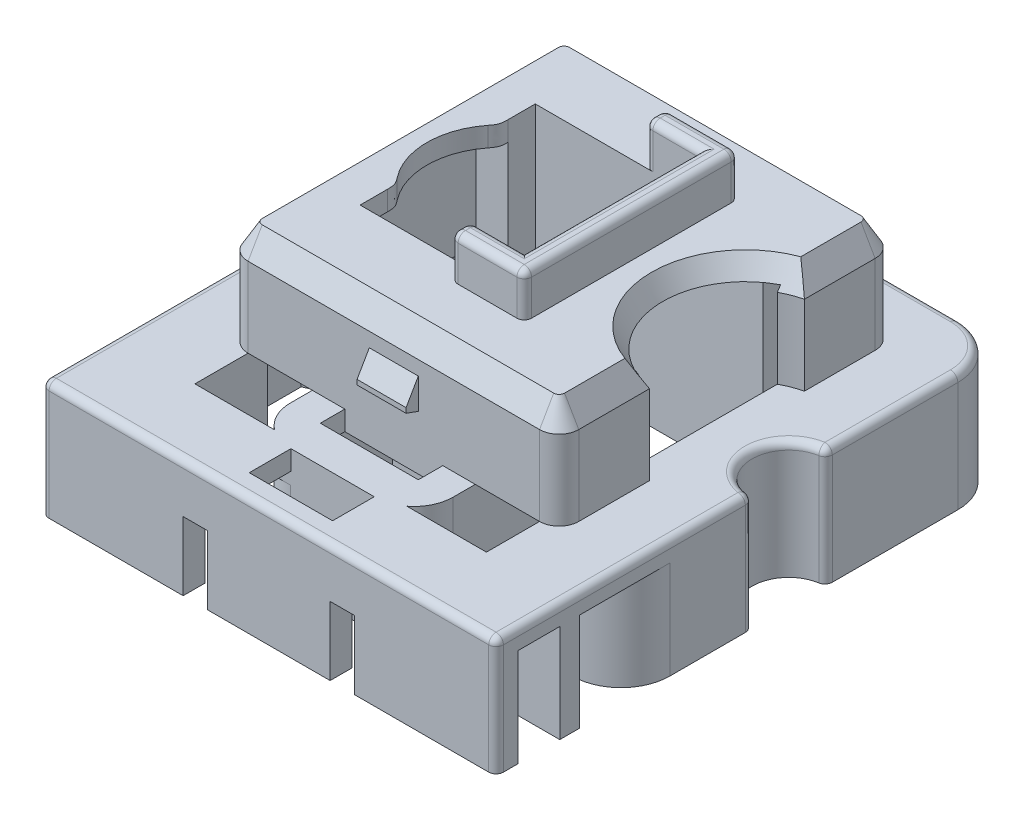
SolidWorks part; units mm, degrees
ref_plane "Front Plane" through (0, 0, 0) normal (0, 0, 1) x (1, 0, 0)
ref_plane "Top Plane" through (0, 0, 0) normal (0, 1, 0) x (1, 0, 0)
ref_plane "Right Plane" through (0, 0, 0) normal (1, 0, 0) x (0, 0, -1)
ref_plane "Floor" through (0, -4, 0) normal (0, -1, 0) x (-1, 0, 0)
sketch "Sketch1" plane through (0, 0, 0) normal (0, 1, 0) x (1, 0, 0)
  line L0 (9.275, -1.5) -> (9.275, -11.95)
  line L1 (-9.275, 8.9) -> (9.275, 8.9)
  line L2 (-9.275, 8.9) -> (-9.275, 1.5)
  line L3 (-9.275, -11.95) -> (9.275, -11.95)
  line L4 (9.275, 8.9) -> (9.275, 1.5)
  line L5 (-9.275, 8.9) -> (9.275, -11.95) construction
  line L6 (-9.275, -11.95) -> (9.275, 8.9) construction
  line L7 (-9.275, -1.5) -> (-9.275, -11.95)
  arc A0 (9.275, 1.5) -> (9.275, -1.5) centre (9.275, 0) ccw
  arc A1 (-9.275, -1.5) -> (-9.275, 1.5) centre (-9.275, 0) ccw
  point P0 (0, -1.525)
  dimension "D4" = 3
  dimension "D5" = 3
  dimension "D1" = 18.55
  dimension "D2" = 20.85
  dimension "D3" = 8.9
extrude "Boss-Extrude1" add sketch "Sketch1" along normal blind 0.8
sketch "Sketch2" plane through (0, 0.8, 0) normal (0, 1, 0) x (1, 0, 0)
  line L0 (6.75, -3.1623) -> (6.75, -6.85)
  line L1 (-6.75, 6.85) -> (6.75, 6.85)
  line L2 (-6.75, 6.85) -> (-6.75, -6.85)
  line L3 (-6.75, -6.85) -> (6.75, -6.85)
  line L4 (6.75, 6.85) -> (6.75, 3.1623)
  line L5 (-6.75, 6.85) -> (6.75, -6.85) construction
  line L6 (-6.75, -6.85) -> (6.75, 6.85) construction
  arc A0 (6.75, 3.1623) -> (6.75, -3.1623) centre (7.5, 0) ccw
  point P0 (0, 0)
  point P7 (13.3281, 0.717)
  point P12 (7.5, 0)
  dimension "D3" = 6.5
  dimension "D1" = 13.5
  dimension "D2" = 13.7
  dimension "D4" = 7.5
extrude "Boss-Extrude2" add sketch "Sketch2" along normal blind 4.25
sketch "Sketch15" plane through (0, 0, 0) normal (0, -1, 0) x (1, 0, 0)
  line L1 (5.95, 6.05) -> (-5.95, 6.05)
  line L2 (5.95, 6.05) -> (5.95, -6.05)
  line L3 (5.95, -6.05) -> (-5.95, -6.05)
  line L4 (-5.95, 6.05) -> (-5.95, -6.05)
  line L5 (5.95, 6.05) -> (-5.95, -6.05) construction
  line L6 (5.95, -6.05) -> (-5.95, 6.05) construction
  point P0 (0, 0)
  dimension "D1" = 11.9
  dimension "D2" = 12.1
extrude "Cut-Extrude3" cut sketch "Sketch15" against normal blind 4.25
ref_plane "Plane2" through (0, 2.3, 0) normal (0, 1, 0) x (1, 0, 0)
sketch "Sketch23" plane through (0, 5.05, 0) normal (0, 1, 0) x (1, 0, 0)
  line L0 (0, -1000) -> (0, 49000) construction
  line L1 (1.9, -1001.0023) -> (1.9, 48998.9977) construction
  line L2 (-2.5, -1002.0635) -> (-2.5, 48997.9365) construction
  line L3 (-4.5, -1002.4785) -> (-4.5, 48997.5215) construction
  line L4 (-1000, 0) -> (49000, 0) construction
  line L6 (-4.65, 3.575) -> (2.05, 3.575)
  line L7 (-4.65, 3.575) -> (-4.65, -3.575)
  line L8 (-4.65, -3.575) -> (2.05, -3.575)
  line L9 (2.05, 3.575) -> (2.05, -3.575)
  line L10 (-4.65, 3.575) -> (2.05, -3.575) construction
  line L11 (-4.65, -3.575) -> (2.05, 3.575) construction
  point P10 (-1.3, 0)
  dimension "D1" = 1.9
  dimension "D2" = 2.5
  dimension "D3" = 2
  dimension "D4" = 7.15
  dimension "D5" = 0.15
  dimension "D6" = 0.15
extrude "Cut-Extrude6" cut sketch "Sketch23" against normal up to surface (0.8 mm away) up to face at (1.7, 4.25, 0)
sketch "Sketch26" plane through (0, 5.05, -5.05) normal (0, -1, 0) x (1, 0, 0)
  line L0 (-0.15, 8.625) -> (-0.15, 9.425)
  line L1 (-4.65, 8.625) -> (2.05, 8.625) construction
  line L2 (-0.15, 9.425) -> (2.85, 9.425)
  line L3 (2.85, 9.425) -> (2.85, 0.675)
  line L4 (2.85, 0.675) -> (-0.15, 0.675)
  line L5 (-0.15, 0.675) -> (-0.15, 1.475)
  line L6 (2.05, 1.475) -> (-4.65, 1.475) construction
  line L7 (-0.15, 1.475) -> (2.05, 1.475)
  line L8 (2.05, 1.475) -> (2.05, 8.625)
  line L9 (2.05, 8.625) -> (-0.15, 8.625)
  line L10 (-0.15, -995.3291) -> (-0.15, 49004.6709) construction
  line L11 (-4.65, 1.475) -> (-4.65, 8.625) construction
  dimension "D1" = 4.5
  dimension "D2" = 0.8
  dimension "D3" = 0.8
  dimension "D4" = 0.8
extrude "Boss-Extrude17" add sketch "Sketch26" against normal blind 1.75
sketch "Sketch5" plane through (0, 5.05, 0) normal (0, 1, 0) x (1, 0, 0)
  circle A0 centre (-2.5, 0) radius 2.75 construction
  circle A1 centre (7.5, 0) radius 2.75 construction
  circle A2 centre (-2.5, 0) radius 3
  point P0 (-2.5, 0)
  dimension "D2" = 5.5
  dimension "D4" = 0.25
  dimension "D1" = 2.5
  dimension "D3" = 10
extrude "Cut-Extrude7" cut sketch "Sketch5" against normal up to surface (0.8 mm away) up to face at (-1.3, 4.25, 0)
sketch "Sketch6" plane through (0, 0, 6.85) normal (0, 0, 1) x (1, 0, 0)
  line L0 (-6.75, 0.8) -> (6.75, 0.8) construction
  line L1 (-1, 2.6) -> (1, 2.6)
  line L2 (-1, 2.6) -> (-1, 2.4)
  line L3 (-1, 2.4) -> (1, 2.4)
  line L4 (1, 2.6) -> (1, 2.4)
  line L5 (-1, 2.6) -> (1, 2.4) construction
  line L6 (-1, 2.4) -> (1, 2.6) construction
  point P0 (0, 2.5)
  dimension "D1" = 1.6
  dimension "D2" = 0.2
  dimension "D3" = 2
extrude "Boss-Extrude4" add sketch "Sketch6" along normal blind 0.5
draft "Draft1" type of draft neutral plane draft angle 60 faces to draft 1 face at (0, 2.6, 7.1) neutral plane through (0, 0, 7.35) neutral plane normal (0, 0, 1) parameters "D1"=60
draft "Draft4" type of draft neutral plane draft angle 20 faces to draft 1 face at (0, 2.4, 7.1) neutral plane through (0, 0, 7.35) neutral plane normal (0, 0, 1) parameters "D1"=20
sketch "Sketch7" plane through (0, 0.8, 0) normal (0, 1, 0) x (1, 0, 0)
  line L0 (-6.75, -6.85) -> (6.75, -6.85) construction
  line L1 (-2, -6.85) -> (2, -6.85)
  line L2 (-2, -6.85) -> (-2, -7.85)
  line L3 (-2, -7.85) -> (2, -7.85)
  line L4 (2, -6.85) -> (2, -7.85)
  line L5 (-2, -6.85) -> (2, -7.85) construction
  line L6 (-2, -7.85) -> (2, -6.85) construction
  point P0 (0, -7.35)
  dimension "D1" = 1
  dimension "D2" = 4
extrude "Cut-Extrude1" cut sketch "Sketch7" against normal through all
mirror "Mirror1" about plane through (0, 0, 0) normal (0, 0, 1) of "Draft4", "Draft1", "Boss-Extrude4", "Cut-Extrude1"
sketch "Sketch8" plane through (0, 0, 0) normal (0, 1, 0) x (1, 0, 0)
  line L1 (9.275, -11.05) -> (-9.275, -11.05)
  line L2 (9.275, -11.05) -> (9.275, -11.95)
  line L3 (9.275, -11.95) -> (-9.275, -11.95)
  line L4 (-9.275, -11.05) -> (-9.275, -11.95)
  line L5 (9.275, -11.05) -> (-9.275, -11.95) construction
  line L6 (9.275, -11.95) -> (-9.275, -11.05) construction
  line L8 (-9.275, -11.95) -> (9.275, -11.95) construction
  point P0 (0, -11.5)
  dimension "D1" = 0.9
extrude "Boss-Extrude5" add sketch "Sketch8" against normal up to surface (4 mm away) up to plane "Floor"
sketch "Sketch9" plane through (0, -4, 0) normal (0, -1, 0) x (-1, 0, 0)
  line L0 (9.275, -11.95) -> (-9.275, -11.95) construction
  line L1 (-9.275, -11.05) -> (9.275, -11.05) construction
  line L7 (-2.5, -11.95) -> (-3.5, -11.95)
  line L8 (-2.5, -11.95) -> (-2.5, -11.05)
  line L9 (-2.5, -11.05) -> (-3.5, -11.05)
  line L10 (-3.5, -11.95) -> (-3.5, -11.05)
  line L11 (-2.5, -11.95) -> (-3.5, -11.05) construction
  line L12 (-2.5, -11.05) -> (-3.5, -11.95) construction
  point P5 (-3, -11.5)
  dimension "D1" = 1
  dimension "D2" = 2.5
extrude "Cut-Extrude2" cut sketch "Sketch9" against normal blind 2.8
mirror "Mirror2" about plane through (0, 0, 0) normal (1, 0, 0) of "Cut-Extrude2"
sketch "Sketch11" plane through (0, 0, 0) normal (0, -1, 0) x (1, 0, 0)
  line L0 (9.275, 11.05) -> (9.275, 1.5) construction
  line L1 (5.95, 9.35) -> (9.275, 9.35)
  line L2 (5.95, 9.35) -> (5.95, 6.05)
  line L3 (9.275, 8.55) -> (6.75, 8.55)
  line L4 (9.275, 9.35) -> (9.275, 8.55)
  line L5 (9.275, 11.05) -> (-9.275, 11.05) construction
  line L6 (6.75, 8.55) -> (6.75, 6.85)
  line L7 (6.75, 6.85) -> (7.275, 6.85)
  line L8 (9.275, 4.85) -> (9.275, 1.5)
  line L9 (5.95, 6.05) -> (7.275, 6.05)
  line L10 (8.475, 4.85) -> (8.475, 2.1564)
  line L11 (9.275, -1.5) -> (9.275, -8.9)
  line L12 (9.275, -1.5) -> (9.275, -8.9) construction
  line L13 (8.475, -8.9) -> (8.475, -2.1564)
  line L14 (9.275, -8.9) -> (-9.275, -8.9) construction
  line L15 (8.475, -8.9) -> (9.275, -8.9)
  line L16 (5.95, -6.05) -> (5.95, 6.05) construction
  line L17 (5.95, 6.05) -> (-5.95, 6.05) construction
  arc A0 (9.275, 1.5) -> (9.275, -1.5) centre (9.275, 0) ccw
  arc A1 (8.475, 2.1564) -> (8.475, -2.1564) centre (9.275, 0) ccw
  arc A2 (7.275, 6.05) -> (8.475, 4.85) centre (7.275, 4.85) cw
  arc A3 (7.275, 6.85) -> (9.275, 4.85) centre (7.275, 4.85) cw
  point P24 (9.275, 6.85)
  dimension "D4" = 3
  dimension "D5" = 4.6
  dimension "D10" = 1.2
  dimension "D11" = 2
  dimension "D1" = 1.7
  dimension "D2" = 0.8
  dimension "D6" = 0.8
  dimension "D7" = 0.8
  dimension "D8" = 0.8
  dimension "D12" = 0.8
extrude "Boss-Extrude6" add sketch "Sketch11" along normal up to surface (4 mm away) up to plane "Floor"
sketch "Sketch12" plane through (0, 0, 0) normal (0, -1, 0) x (1, 0, 0)
  line L1 (5.95, 11.05) -> (6.75, 11.05)
  line L2 (5.95, 11.05) -> (5.95, 9.35)
  line L3 (5.95, 9.35) -> (6.75, 9.35)
  line L4 (6.75, 11.05) -> (6.75, 9.35)
  line L5 (9.275, 11.05) -> (-9.275, 11.05) construction
  line L6 (9.275, 9.35) -> (5.95, 9.35) construction
  line L7 (5.95, 9.35) -> (5.95, 6.05) construction
  line L8 (6.75, 6.85) -> (6.75, 8.55) construction
extrude "Boss-Extrude7" add sketch "Sketch12" along normal blind 1.5
mirror "Mirror3" about plane through (0, 0, 0) normal (1, 0, 0) of "Boss-Extrude7", "Boss-Extrude6"
sketch "Sketch19" plane through (0, 0, 0) normal (0, -1, 0) x (1, 0, 0)
  line L0 (8.475, -8.9) -> (-8.475, -8.9) construction
  line L1 (-4.65, -3.575) -> (4.65, -3.575)
  line L2 (-4.65, -3.575) -> (-4.65, -8.9)
  line L3 (-4.65, -8.9) -> (4.65, -8.9)
  line L4 (4.65, -3.575) -> (4.65, -8.9)
  line L5 (-4.65, -3.575) -> (4.65, -8.9) construction
  line L6 (-4.65, -8.9) -> (4.65, -3.575) construction
  line L7 (-4.65, -3.575) -> (2.05, -3.575) construction
  line L8 (-3.85, -8.1) -> (3.85, -8.1)
  line L9 (-3.85, -8.1) -> (-3.85, -4.375)
  line L10 (-3.85, -4.375) -> (3.85, -4.375)
  line L11 (3.85, -8.1) -> (3.85, -4.375)
  line L12 (-3.85, -8.1) -> (3.85, -4.375) construction
  line L13 (-3.85, -4.375) -> (3.85, -8.1) construction
  line L14 (-4.65, -2.0922) -> (-4.65, -3.575) construction
  point P0 (0, -6.2375)
  point P7 (0, -8.9)
  point P9 (0, -6.2375)
  dimension "D3" = 0.8
  dimension "D4" = 0.8
sketch "Sketch13" plane through (0, 0, 0) normal (0, -1, 0) x (1, 0, 0)
  line L0 (8.475, -8.9) -> (-8.475, -8.9) construction
  line L1 (8.475, -8.1) -> (-8.475, -8.1)
  line L2 (8.475, -8.1) -> (8.475, -8.9)
  line L3 (8.475, -8.9) -> (-8.475, -8.9)
  line L4 (-8.475, -8.1) -> (-8.475, -8.9)
  line L5 (8.475, -8.1) -> (-8.475, -8.9) construction
  line L6 (8.475, -8.9) -> (-8.475, -8.1) construction
  point P0 (0, -8.5)
  point P7 (0, -8.9)
  dimension "D1" = 0.8
extrude "Boss-Extrude8" add sketch "Sketch13" along normal up to surface (4 mm away) up to plane "Floor"
fillet "Fillet6" radius 1 2 edges at (-4.65, 4.65, 2.0922) (-4.65, 4.65, -2.0922) conic rho 0.65
fillet "Fillet1" radius 1.2 2 edges at (8.475, -2, -8.1) (-8.475, -2, -8.1)
fillet "Fillet2" radius 2 2 edges at (9.275, -1.6, -8.9) (-9.275, -1.6, -8.9)
fillet "Fillet3" radius 0.3 30 edges at (9.275, 0.8, -4.2) (8.6892, 0.8, -8.3142) (0, 0.8, -8.9) (-8.6892, 0.8, -8.3142) (7.775, 0.8, 0) (-7.775, 0.8, 0) (-9.275, 0.8, 6.725) (0, 0.8, 11.95) (9.275, 0.8, 6.725) (-9.275, 0.8, -4.2) (-9.275, -1.6, -1.5) (-9.275, -1.6, 1.5) (9.275, -1.6, -1.5) (9.275, -1.6, 1.5) (-9.275, -1.6, 11.95) (9.275, -1.6, 11.95) (2.05, 6.8, 0) (0.95, 6.8, -3.575) (-0.15, 6.8, -3.975) (1.35, 6.8, -4.375) (2.85, 6.8, 0) (1.35, 6.8, 4.375) (-0.15, 6.8, 3.975) (0.95, 6.8, 3.575) (-0.15, 5.925, -3.575) (-0.15, 5.925, -4.375) (-0.15, 5.925, 3.575) (-0.15, 5.925, 4.375) (2.85, 5.925, -4.375) (2.85, 5.925, 4.375)
fillet "Fillet5" radius 0.8 4 edges at (-6.75, 2.925, -6.85) (6.75, 2.925, -6.85) (-6.75, 2.925, 6.85) (6.75, 2.925, 6.85)
chamfer "Chamfer1" distance 1 angle 30 10 edges at (6.5157, 5.05, -6.6157) (0, 5.05, -6.85) (-6.5157, 5.05, -6.6157) (-6.75, 5.05, 0) (-6.5157, 5.05, 6.6157) (6.75, 5.05, -4.6061) (0, 5.05, 6.85) (6.75, 5.05, 4.6061) (6.5157, 5.05, 6.6157) (4.25, 5.05, 0) first distance on face at (6.4328, 2.925, -6.5328) first distance on face at (0, 2.842, -6.85) first distance on face at (-6.4328, 2.925, -6.5328) first distance on face at (-6.75, 2.925, 0) first distance on face at (-6.4328, 2.925, 6.5328) first distance on face at (6.75, 2.925, -4.6061) first distance on face at (0, 1.6625, 6.85) first distance on face at (6.75, 2.925, 4.6061) first distance on face at (6.4328, 2.925, 6.5328) first distance on face at (5.8225, 2.725, 0)
sketch "Sketch14" plane through (0, 0, 0) normal (0, -1, 0) x (1, 0, 0)
  line L0 (9.275, 9.35) -> (6.75, 9.35) construction
  line L1 (-1.725, 9.35) -> (1.725, 9.35)
  line L2 (-3.325, 7.75) -> (-3.325, 3.575)
  line L3 (-3.325, 3.575) -> (3.325, 3.575)
  line L4 (3.325, 7.75) -> (3.325, 3.575)
  line L5 (-3.325, 9.35) -> (3.325, 3.575) construction
  line L6 (-3.325, 3.575) -> (3.325, 9.35) construction
  line L7 (2.05, 3.575) -> (-4.65, 3.575) construction
  line L8 (-1.725, 8.55) -> (1.725, 8.55)
  line L9 (-2.525, 7.75) -> (-2.525, 4.375)
  line L10 (-2.525, 4.375) -> (2.525, 4.375)
  line L11 (2.525, 7.75) -> (2.525, 4.375)
  line L12 (-2.525, 8.55) -> (2.525, 4.375) construction
  line L13 (-2.525, 4.375) -> (2.525, 8.55) construction
  arc A0 (-1.725, 9.35) -> (-3.325, 7.75) centre (-1.725, 7.75) ccw
  arc A1 (1.725, 9.35) -> (3.325, 7.75) centre (1.725, 7.75) cw
  arc A2 (-1.725, 8.55) -> (-2.525, 7.75) centre (-1.725, 7.75) ccw
  arc A3 (1.725, 8.55) -> (2.525, 7.75) centre (1.725, 7.75) cw
  point P0 (0, 6.4625)
  point P10 (0, 6.4625)
  dimension "D5" = 1.6
  dimension "D6" = 0.8
  dimension "D1" = 6.65
  dimension "D3" = 0.8
  dimension "D4" = 0.8
extrude "Boss-Extrude9" add sketch "Sketch14" along normal up to surface (4 mm away) up to plane "Floor"
sketch "Sketch16" plane through (0, 0, 0) normal (0, -1, 0) x (1, 0, 0)
  line L8 (-3.325, 6.05) -> (-3.325, 3.575)
  line L9 (-2.525, 6.05) -> (-3.325, 6.05)
  line L10 (-2.525, 4.375) -> (-2.525, 6.05)
  line L11 (2.525, 4.375) -> (-2.525, 4.375)
  line L12 (2.525, 6.05) -> (2.525, 4.375)
  line L13 (3.325, 6.05) -> (2.525, 6.05)
  line L14 (3.325, 3.575) -> (3.325, 6.05)
  line L15 (-3.325, 3.575) -> (3.325, 3.575)
  line L16 (-3.325, 6.05) -> (-3.325, 3.575)
  line L17 (-2.525, 6.05) -> (-3.325, 6.05)
  line L18 (-2.525, 4.375) -> (-2.525, 6.05)
  line L19 (2.525, 4.375) -> (-2.525, 4.375)
  line L20 (2.525, 6.05) -> (2.525, 4.375)
  line L21 (3.325, 6.05) -> (2.525, 6.05)
  line L22 (3.325, 3.575) -> (3.325, 6.05)
  line L23 (-3.325, 3.575) -> (3.325, 3.575)
  dimension "D1" = 0
extrude "Boss-Extrude10" add sketch "Sketch16" against normal up to surface (4.25 mm away) up to face at (-3.0281, 4.25, 0.2928)
sketch "Sketch17" plane through (0, 0, 0) normal (0, -1, 0) x (1, 0, 0)
  line L0 (5.95, 11.05) -> (-5.95, 11.05) construction
  line L1 (-1.7, 11.05) -> (1.7, 11.05)
  line L2 (-1.7, 11.05) -> (-1.7, 9.35)
  line L3 (-1.7, 9.35) -> (1.7, 9.35)
  line L4 (1.7, 11.05) -> (1.7, 9.35)
  line L5 (-1.7, 11.05) -> (1.7, 9.35) construction
  line L6 (-1.7, 9.35) -> (1.7, 11.05) construction
  line L7 (1.725, 9.35) -> (-1.725, 9.35) construction
  point P0 (0, 10.2)
  dimension "D1" = 3.4
extrude "Cut-Extrude4" cut sketch "Sketch17" against normal through all
sketch "Sketch18" plane through (0, 0, 11.05) normal (0, 0, -1) x (-1, 0, 0)
  line L1 (1.4, -3.1) -> (-1.4, -3.1)
  line L2 (1.4, -3.1) -> (1.4, -3.3)
  line L3 (1.4, -3.3) -> (-1.4, -3.3)
  line L4 (-1.4, -3.1) -> (-1.4, -3.3)
  line L5 (1.4, -3.1) -> (-1.4, -3.3) construction
  line L6 (1.4, -3.3) -> (-1.4, -3.1) construction
  line L7 (-6.75, -1.5) -> (-5.95, -1.5) construction
  point P0 (0, -3.2)
  dimension "D1" = 1.6
  dimension "D2" = 0.2
  dimension "D3" = 2.8
extrude "Boss-Extrude11" add sketch "Sketch18" along normal blind 0.25
draft "Draft2" type of draft neutral plane draft angle 60 faces to draft 1 face at (0, -3.3, 10.925) neutral plane through (0, 0, 10.8) neutral plane normal (0, 0, -1) parameters "D1"=60
draft "Draft3" type of draft neutral plane draft angle 20 faces to draft 1 face at (0, -3.1, 10.925) neutral plane through (0, 0, 10.8) neutral plane normal (0, 0, -1) parameters "D1"=20
ref_plane "Plane4" through (0, 0, 10.2) normal (0, 0, -1) x (-1, 0, 0)
mirror "Mirror4" about plane through (0, 0, 10.2) normal (0, 0, -1) of "Draft3", "Draft2", "Boss-Extrude11"
extrude "Boss-Extrude12" add sketch "Sketch19" along normal up to surface (4 mm away) up to plane "Floor"
sketch "Sketch20" plane through (0, 0, 0) normal (0, -1, 0) x (1, 0, 0)
  line L8 (4.65, -6.05) -> (4.65, -3.575)
  line L9 (3.85, -6.05) -> (4.65, -6.05)
  line L10 (3.85, -4.375) -> (3.85, -6.05)
  line L11 (-3.85, -4.375) -> (3.85, -4.375)
  line L12 (-3.85, -6.05) -> (-3.85, -4.375)
  line L13 (-4.65, -6.05) -> (-3.85, -6.05)
  line L14 (-4.65, -3.575) -> (-4.65, -6.05)
  line L15 (4.65, -3.575) -> (-4.65, -3.575)
  line L16 (4.65, -6.05) -> (4.65, -3.575)
  line L17 (3.85, -6.05) -> (4.65, -6.05)
  line L18 (3.85, -4.375) -> (3.85, -6.05)
  line L19 (-3.85, -4.375) -> (3.85, -4.375)
  line L20 (-3.85, -6.05) -> (-3.85, -4.375)
  line L21 (-4.65, -6.05) -> (-3.85, -6.05)
  line L22 (-4.65, -3.575) -> (-4.65, -6.05)
  line L23 (4.65, -3.575) -> (-4.65, -3.575)
  dimension "D1" = 0
extrude "Boss-Extrude13" add sketch "Sketch20" against normal up to surface (4.25 mm away) up to face at (-0.7856, 4.25, 1.1996)
sketch "Sketch21" plane through (0, 0, 0) normal (0, -1, 0) x (1, 0, 0)
  line L0 (2.7, 11.05) -> (2.7, 9.0186) construction
  line L1 (5.95, 11.05) -> (1.7, 11.05) construction
  line L2 (1.7, 9.35) -> (1.7, 11.05) construction
  line L3 (2.7, 9.0186) -> (5.95, 9.0186)
  line L9 (5.95, 11.05) -> (1.7, 11.05)
  line L10 (1.7, 11.05) -> (1.7, 9.35)
  line L11 (1.7, 9.35) -> (1.725, 9.35)
  line L12 (3.325, 7.75) -> (3.325, 6.05)
  line L13 (3.325, 6.05) -> (5.95, 6.05)
  line L14 (5.95, 6.05) -> (5.95, 11.05)
  line L18 (3.325, 7.75) -> (3.325, 6.05)
  line L19 (3.325, 6.05) -> (5.95, 6.05)
  line L20 (5.95, 6.05) -> (5.95, 9.0186)
  arc A0 (3.325, 7.75) -> (1.725, 9.35) centre (1.725, 7.75) ccw construction
  arc A2 (3.325, 7.75) -> (1.725, 9.35) centre (1.725, 7.75) ccw
  arc A3 (3.325, 7.75) -> (2.7, 9.0186) centre (1.725, 7.75) ccw
  dimension "D1" = 1
  dimension "D2" = 0
extrude "Cut-Extrude5" cut sketch "Sketch21" against normal up to surface (0.8 mm away) up to face at (0, 0.8, 10.2)
sketch "Sketch22" plane through (0, 0, 0) normal (0, -1, 0) x (1, 0, 0)
  line L0 (1.725, 9.35) -> (5.95, 9.35)
  line L5 (2.7, 9.0186) -> (5.95, 9.0186)
  line L6 (5.95, 9.0186) -> (5.95, 11.05)
  line L7 (5.95, 11.05) -> (1.7, 11.05)
  line L8 (1.7, 11.05) -> (1.7, 9.35)
  line L9 (1.7, 9.35) -> (1.725, 9.35)
  line L10 (2.7, 9.0186) -> (5.95, 9.0186)
  line L11 (5.95, 9.0186) -> (5.95, 9.35)
  arc A1 (2.7, 9.0186) -> (1.725, 9.35) centre (1.725, 7.75) ccw
  arc A2 (2.7, 9.0186) -> (1.725, 9.35) centre (1.725, 7.75) ccw
  dimension "D1" = 0
extrude "Boss-Extrude14" add sketch "Sketch22" along normal blind 0.5
mirror "Mirror5" about plane through (0, 0, 0) normal (1, 0, 0) of "Boss-Extrude14", "Cut-Extrude5"
chamfer "Chamfer2" distance 0.5 angle 30 2 edges at (4.6375, 0.8, 6.05) (-4.6375, 0.8, 6.05) first distance on face at (4.6375, 2.525, 6.05) first distance on face at (-4.6375, 0.8, 6.45)
sketch "Sketch24" plane through (0, 4.25, 0) normal (0, -1, 0) x (1, 0, 0)
  line L0 (2.05, 3.575) -> (2.05, -3.575) construction
  line L1 (2.05, 1.075) -> (3.325, 1.075)
  line L2 (2.05, 1.075) -> (2.05, 3.575)
  line L3 (2.05, 3.575) -> (3.325, 3.575)
  line L4 (3.325, 1.075) -> (3.325, 3.575)
  dimension "D1" = 2.5
extrude "Boss-Extrude15" add sketch "Sketch24" along normal up to surface (8.25 mm away) up to plane "Floor"
sketch "Sketch25" plane through (0, 4.25, 0) normal (0, -1, 0) x (1, 0, 0)
  line L0 (-4.65, -2.4653) -> (-5.95, -2.4653)
  line L9 (-4.65, 2.4653) -> (-4.65, 3.575)
  line L10 (-4.65, 3.575) -> (-3.325, 3.575)
  line L11 (-3.325, 3.575) -> (-3.325, 6.05)
  line L12 (-3.325, 6.05) -> (-5.95, 6.05)
  line L13 (-5.95, 6.05) -> (-5.95, -6.05)
  line L14 (-5.95, -6.05) -> (-4.65, -6.05)
  line L15 (-4.65, -6.05) -> (-4.65, -3.575)
  line L17 (-4.65, -3.575) -> (-4.65, -2.4653)
  line L22 (-5.95, -2.4653) -> (-5.95, -6.05)
  line L23 (-5.95, -6.05) -> (-4.65, -6.05)
  line L24 (-4.65, -6.05) -> (-4.65, -3.575)
  line L26 (-4.65, -3.575) -> (-4.65, -2.4653)
  arc A1 (-4.8625, 1.8489) -> (-4.8625, -1.8489) centre (-2.5, 0) ccw
  spline S2 degree 2 poles (-748.2714, -666.988) (-11.4668, -8.1889) (-4.7633, 1.9848) (-4.7116, 2.0633) (-4.6871, 2.1335) (-4.6638, 2.2003) (-4.6556, 2.2972) (-3.7384, 13.1006) (-152.9575, 991.4046) knots -43.936804 -43.936804 -43.936804 0.25 0.25 0.5 0.5 0.75 0.75 41.674386 41.674386 41.674386 only from (-4.8625, 1.8489) to (-4.65, 2.4653)
  spline S3 degree 2 poles (-177.8705, -987.3482) (-3.6644, -14.4404) (-4.6556, -2.2971) (-4.6633, -2.2035) (-4.6873, -2.1331) (-4.7101, -2.0661) (-4.7633, -1.9848) (-10.6994, 7.0882) (-731.1525, 685.5367) knots -43.936804 -43.936804 -43.936804 0.25 0.25 0.5 0.5 0.75 0.75 41.674386 41.674386 41.674386 only from (-4.65, -2.4653) to (-4.8625, -1.8489)
  dimension "D1" = 0
extrude "Boss-Extrude16" add sketch "Sketch25" along normal up to surface (8.25 mm away) up to plane "Floor"
